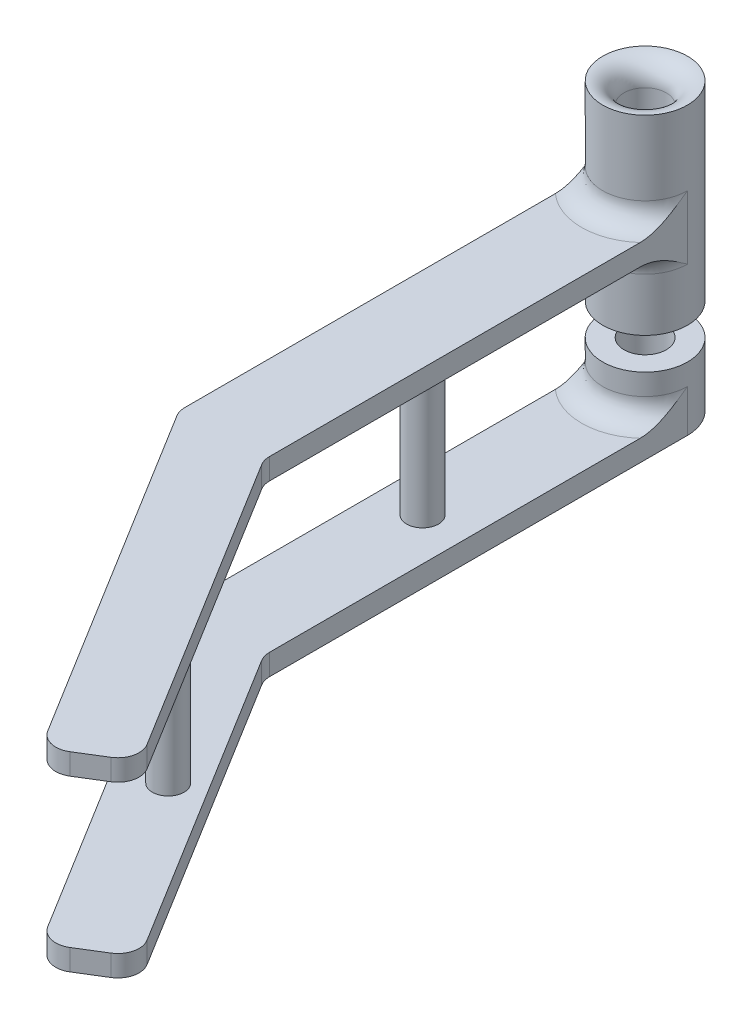
SolidWorks part; units mm, degrees
material "ABS"
ref_plane "Front Plane" through (0, 0, 0) normal (0, 0, 1) x (1, 0, 0)
ref_plane "Top Plane" through (0, 0, 0) normal (0, 1, 0) x (1, 0, 0)
ref_plane "Right Plane" through (0, 0, 0) normal (1, 0, 0) x (0, 0, -1)
sketch "Sketch1" plane through (0, 0, 0) normal (0, 1, 0) x (1, 0, 0)
  circle A0 centre (0, 0) radius 30
  dimension "D1" = 60
extrude "Boss-Extrude1" add sketch "Sketch1" along normal blind 200
sketch "Sketch2" plane through (0, 200, 0) normal (0, 1, 0) x (1, 0, 0)
  circle A0 centre (0, -50) radius 4
  circle A2 centre (0, 0) radius 30 construction
  dimension "D1" = 8
  dimension "D2" = 50
extrude "Boss-Extrude2" add sketch "Sketch2" against normal blind 80 from offset 60 separate body offset against normal yes
sketch "Sketch4" plane through (0, 140, 0) normal (0, 1, 0) x (1, 0, 0)
  line L6 (-2.9328, -47.28) -> (40.9159, 0)
  line L7 (2.9328, -52.72) -> (51.8267, 0)
  line L8 (40.9159, 0) -> (6, 37.6481)
  line L9 (51.8267, 0) -> (11.8657, 43.0881)
  line L10 (6, 37.6481) -> (11.8657, 43.0881)
  circle A0 centre (0, -50) radius 4 construction
  circle A1 centre (0, 0) radius 30 construction
  arc A2 (2.9328, -52.72) -> (-2.9328, -47.28) centre (0, -50) ccw
  dimension "D2" = 6
  dimension "D4" = 8
  dimension "D5" = 8
  dimension "D6" = 8
extrude "Boss-Extrude3" add sketch "Sketch4" against normal blind 10 from offset 10 offset against normal yes
sketch "Sketch5" plane through (0, 60, 0) normal (0, -1, 0) x (1, 0, 0)
  line L0 (6, -37.6481) -> (11.8657, -43.0881) construction
  line L1 (40.9159, 0) -> (6, -37.6481) construction
  line L2 (51.8267, 0) -> (11.8657, -43.0881) construction
  line L3 (2.9328, 52.72) -> (51.8267, 0) construction
  line L4 (-2.9328, 47.28) -> (40.9159, 0) construction
  line L5 (6, -37.6481) -> (11.8657, -43.0881)
  line L6 (40.9159, 0) -> (6, -37.6481)
  line L7 (51.8267, 0) -> (11.8657, -43.0881)
  line L8 (2.9328, 52.72) -> (51.8267, 0)
  line L9 (-2.9328, 47.28) -> (40.9159, 0)
  arc A0 (-2.9328, 47.28) -> (2.9328, 52.72) centre (0, 50) ccw construction
  arc A1 (-2.9328, 47.28) -> (2.9328, 52.72) centre (0, 50) ccw
extrude "Boss-Extrude4" add sketch "Sketch5" against normal blind 10 from offset 10 offset against normal yes
sketch "Sketch7" plane through (0, 140, 0) normal (0, 1, 0) x (1, 0, 0)
  circle A0 centre (0, -50) radius 4
extrude "Cut-Extrude1" cut sketch "Sketch7" against normal blind 12 from offset 34 offset against normal yes
sketch "Sketch8" plane through (0, 140, 0) normal (0, 1, 0) x (1, 0, 0)
  circle A0 centre (0, -50) radius 2
  dimension "D1" = 4
extrude "Cut-Extrude2" cut sketch "Sketch8" against normal blind 70
sketch "Sketch9" plane through (0, 140, 0) normal (0, 1, 0) x (1, 0, 0)
  circle A0 centre (0, -50) radius 2
extrude "Boss-Extrude6" add sketch "Sketch9" against normal blind 70 from offset 0.1
sketch "Sketch11" plane through (0, 140.1, 0) normal (0, 1, 0) x (1, 0, 0)
  line L0 (-0.975, -51.7462) -> (-0.975, -48.2538)
  line L1 (0.975, -48.2538) -> (0.975, -51.7462)
  circle A0 centre (0, -50) radius 2 construction
  circle A1 centre (0, -50) radius 2 construction
  arc A2 (-0.975, -48.2538) -> (-0.975, -51.7462) centre (0, -50) ccw
  arc A3 (0.975, -48.2538) -> (0.975, -51.7462) centre (0, -50) cw
  dimension "D3" = 2
  dimension "D4" = 2
  dimension "D1" = 1.95
  dimension "D2" = 0.975
extrude "Cut-Extrude4" cut sketch "Sketch11" against normal blind 35 from offset 30 offset against normal yes
sketch "Sketch12" plane through (0, 140.1, 0) normal (0, 1, 0) x (1, 0, 0)
  line L1 (-0.5, -48.8) -> (0.5, -48.8)
  line L2 (-0.5, -48.8) -> (-0.5, -51.2)
  line L3 (-0.5, -51.2) -> (0.5, -51.2)
  line L4 (0.5, -48.8) -> (0.5, -51.2)
  dimension "D1" = 0.5
  dimension "D2" = 0.5
  dimension "D3" = 1.2
  dimension "D4" = 2.4
extrude "Cut-Extrude5" cut sketch "Sketch12" against normal blind 20
sketch "Sketch14" plane through (0, 200, 0) normal (0, 1, 0) x (1, 0, 0)
  circle A0 centre (0, 0) radius 30
extrude "Cut-Extrude6" cut sketch "Sketch14" against normal blind 200
sketch "Sketch15" plane through (0, 140, 0) normal (0, 1, 0) x (1, 0, 0)
  circle A0 centre (0, -50) radius 2
extrude "Cut-Extrude7" cut sketch "Sketch15" against normal blind 70 and the other way blind 200
sketch "Sketch18" plane through (0, 130, 0) normal (0, 1, 0) x (1, 0, 0)
  line L5 (2.9328, -52.72) -> (51.8267, 0)
  line L6 (51.8267, 0) -> (11.8657, 43.0881)
  line L7 (11.8657, 43.0881) -> (6, 37.6481)
  line L8 (6, 37.6481) -> (40.9159, 0)
  line L9 (40.9159, 0) -> (-2.9328, -47.28)
  line L10 (2.9328, -52.72) -> (51.8267, 0)
  line L11 (51.8267, 0) -> (11.8657, 43.0881)
  line L12 (11.8657, 43.0881) -> (6, 37.6481)
  line L13 (6, 37.6481) -> (40.9159, 0)
  line L14 (40.9159, 0) -> (-2.9328, -47.28)
  arc A1 (2.9328, -52.72) -> (-2.9328, -47.28) centre (0, -50) ccw
  arc A2 (2.9328, -52.72) -> (-2.9328, -47.28) centre (0, -50) ccw
  dimension "D1" = 0
extrude "Cut-Extrude9" cut sketch "Sketch18" against normal blind 5
sketch "Sketch20" plane through (0, 125, 0) normal (0, 1, 0) x (1, 0, 0)
  line L5 (2.9328, -52.72) -> (51.8267, 0)
  line L6 (51.8267, 0) -> (11.8657, 43.0881)
  line L7 (11.8657, 43.0881) -> (6, 37.6481)
  line L8 (6, 37.6481) -> (40.9159, 0)
  line L9 (40.9159, 0) -> (-2.9328, -47.28)
  line L10 (2.9328, -52.72) -> (51.8267, 0)
  line L11 (51.8267, 0) -> (11.8657, 43.0881)
  line L12 (11.8657, 43.0881) -> (6, 37.6481)
  line L13 (6, 37.6481) -> (40.9159, 0)
  line L14 (40.9159, 0) -> (-2.9328, -47.28)
  arc A1 (2.9328, -52.72) -> (-2.9328, -47.28) centre (0, -50) ccw
  arc A2 (2.9328, -52.72) -> (-2.9328, -47.28) centre (0, -50) ccw
  dimension "D1" = 0
extrude "Cut-Extrude10" cut sketch "Sketch20" against normal blind 5
ref_plane "Plane1" through (0, 100, 0) normal (0, 1, 0) x (1, 0, 0)
sketch "Sketch22" plane through (0, 80, 0) normal (0, 1, 0) x (1, 0, 0)
  line L6 (6, 37.6481) -> (40.9159, 0)
  line L7 (40.9159, 0) -> (-2.9328, -47.28)
  line L8 (2.9328, -52.72) -> (51.8267, 0)
  line L9 (51.8267, 0) -> (11.8657, 43.0881)
  line L10 (11.8657, 43.0881) -> (6, 37.6481)
  line L11 (6, 37.6481) -> (40.9159, 0)
  line L12 (40.9159, 0) -> (-2.9328, -47.28)
  line L13 (2.9328, -52.72) -> (51.8267, 0)
  line L14 (51.8267, 0) -> (11.8657, 43.0881)
  line L15 (11.8657, 43.0881) -> (6, 37.6481)
  arc A1 (2.9328, -52.72) -> (-2.9328, -47.28) centre (0, -50) ccw
  arc A2 (2.9328, -52.72) -> (-2.9328, -47.28) centre (0, -50) ccw
  dimension "D1" = 0
extrude "Cut-Extrude11" cut sketch "Sketch22" against normal blind 10
sketch "Sketch24" plane through (0, 60, 0) normal (0, -1, 0) x (1, 0, 0)
  circle A0 centre (0, 50) radius 4 construction
  circle A1 centre (0, 50) radius 4
extrude "Cut-Extrude12" cut sketch "Sketch24" against normal blind 10
sketch "Sketch25" plane through (0, 140, 0) normal (0, 1, 0) x (1, 0, 0)
  circle A0 centre (0, -50) radius 4 construction
  circle A1 centre (0, -50) radius 4
extrude "Cut-Extrude13" cut sketch "Sketch25" against normal blind 10
fillet "Fillet10" radius 2 1 edges at (0, 130, 52)
sketch "Sketch28" plane through (0, 70, 0) normal (0, -1, 0) x (1, 0, 0)
  line L1 (-7.7664, 66.8906) -> (11.2683, 66.8906)
  line L2 (-7.7664, 66.8906) -> (-7.7664, 36.4785)
  line L3 (-7.7664, 36.4785) -> (11.2683, 36.4785)
  line L4 (11.2683, 66.8906) -> (11.2683, 36.4785)
extrude "Cut-Extrude14" cut sketch "Sketch28" against normal blind 30
sketch "Sketch30" plane through (0, 106, 0) normal (0, -1, 0) x (1, 0, 0)
  line L1 (-4, 50) -> (4, 50)
  line L2 (-4, 50) -> (-4, 90)
  line L4 (4, 50) -> (4, 90)
  line L9 (-4, 90) -> (4, 90)
  line L10 (-4, 90) -> (17.0114, 124.037)
  line L11 (4, 90) -> (22.804, 120.4612)
  line L12 (17.0114, 124.037) -> (22.804, 120.4612)
  circle A0 centre (0, 50) radius 4 construction
  dimension "D1" = 8
  dimension "D2" = 40
  dimension "D4" = 40
extrude "Boss-Extrude7" add sketch "Sketch30" along normal blind 2 from offset 15 contours L12 L10 L9 L11 | L9 L4 L1 L2 region at (9.8901, 106, 106.1411) offset against normal yes
sketch "Sketch31" plane through (0, 106, 0) normal (0, -1, 0) x (1, 0, 0)
  line L1 (-11.9647, 54.8867) -> (12.9558, 54.8867)
  line L2 (-11.9647, 54.8867) -> (-11.9647, 44.889)
  line L3 (-11.9647, 44.889) -> (12.9558, 44.889)
  line L4 (12.9558, 54.8867) -> (12.9558, 44.889)
extrude "Cut-Extrude15" cut sketch "Sketch31" against normal blind 6
sketch "Sketch32" plane through (0, 112, 0) normal (0, -1, 0) x (1, 0, 0)
  arc A0 (2, 50) -> (-2, 50) centre (0, 50) ccw construction
  circle A1 centre (0, 50) radius 4 construction
  circle A2 centre (0, 50) radius 2 construction
  circle A3 centre (0, 50) radius 4
  circle A4 centre (0, 50) radius 2
  arc A5 (2, 50) -> (-2, 50) centre (0, 50) ccw
  circle M1 centre (0, 50) radius 4
  circle M2 centre (0, 50) radius 2
extrude "Boss-Extrude8" add sketch "Sketch32" along normal blind 6 from offset 3 separate body contours A4 M1 M2 region at (-3.8869, 112, 50)
sketch "Sketch33" plane through (0, 103, 0) normal (0, -1, 0) x (1, 0, 0)
  line L0 (-2, 50) -> (2, 50) construction
  circle A0 centre (0, 50) radius 2
extrude "Boss-Extrude9" add sketch "Sketch33" against normal blind 2
sketch "Sketch34" plane through (0, 103, 0) normal (0, -1, 0) x (1, 0, 0)
  line L0 (4, 50) -> (4, 90) construction
  line L1 (4, 90) -> (22.804, 120.4612) construction
  line L2 (17.0114, 124.037) -> (22.804, 120.4612) construction
  line L3 (-4, 90) -> (17.0114, 124.037) construction
  line L4 (-4, 50) -> (-4, 90) construction
  line L5 (4, 50) -> (4, 90)
  line L6 (4, 90) -> (22.804, 120.4612)
  line L7 (17.0114, 124.037) -> (22.804, 120.4612)
  line L8 (-4, 90) -> (17.0114, 124.037)
  line L9 (-4, 50) -> (-4, 90)
  circle M1 centre (0, 50) radius 4
extrude "Boss-Extrude10" add sketch "Sketch34" against normal blind 2 contours L9 L5 L6 L7 L8 M1 region at (0, 103, 54.7874)
sketch "Sketch35" plane through (0, 121, 0) normal (0, 1, 0) x (1, 0, 0)
  line L0 (-2, -50) -> (2, -50) construction
  circle A0 centre (0, -50) radius 2
extrude "Cut-Extrude16" cut sketch "Sketch35" against normal blind 2
sketch "Sketch36" plane through (0, 119, 0) normal (0, -1, 0) x (1, 0, 0)
  line L0 (17.0114, 124.037) -> (22.804, 120.4612) construction
  line L1 (-4, 50) -> (-4, 90) construction
  line L2 (-4, 90) -> (17.0114, 124.037) construction
  circle A0 centre (0, 71) radius 1.5
  circle A1 centre (9.9094, 104.9174) radius 1.5
  arc A2 (-4, 50) -> (4, 50) centre (0, 50) ccw construction
  point P9 (0, 46)
  dimension "D1" = 3
  dimension "D2" = 3
  dimension "D5" = 4
  dimension "D6" = 4
  dimension "D3" = 20
  dimension "D4" = 25
extrude "Boss-Extrude11" add sketch "Sketch36" along normal blind 14
fillet "Fillet11" radius 2 11 edges at (0, 105, 54) (0, 119, 54) (0, 121, 54) (-4, 120, 90) (-4, 104, 90) (4, 104, 90) (4, 120, 90) (22.804, 104, 120.4612) (17.0114, 104, 124.037) (17.0114, 120, 124.037) (22.804, 120, 120.4612)
